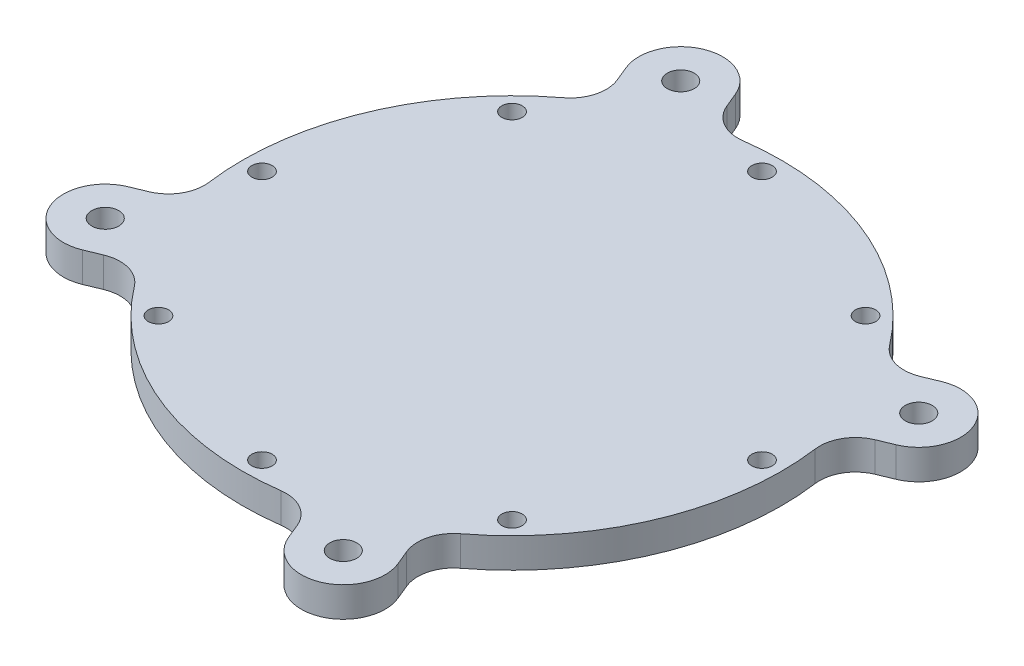
SolidWorks part; units mm, degrees
material "6061-T6 (SS)"
ref_plane "Front Plane" through (0, 0, 0) normal (0, 0, 1) x (1, 0, 0)
ref_plane "Top Plane" through (0, 0, 0) normal (0, 1, 0) x (1, 0, 0)
ref_plane "Right Plane" through (0, 0, 0) normal (1, 0, 0) x (0, 0, -1)
sketch "Sketch1" plane through (0, 0, 0) normal (0, 1, 0) x (1, 0, 0)
  circle A0 centre (0, 0) radius 45
  circle A1 centre (0, 41.75) radius 1.5
  circle A2 centre (29.5217, 29.5217) radius 1.5
  circle A3 centre (41.75, 0) radius 1.5
  circle A4 centre (29.5217, -29.5217) radius 1.5
  circle A5 centre (0, -41.75) radius 1.5
  circle A6 centre (-29.5217, -29.5217) radius 1.5
  circle A7 centre (-41.75, 0) radius 1.5
  circle A8 centre (-29.5217, 29.5217) radius 1.5
  point P22 (0, 0)
  dimension "D1" = 8
extrude "Boss-Extrude2" add sketch "Sketch1" along normal blind 5
sketch "Sketch9" plane through (0, 0, 0) normal (0, -1, 0) x (1, 0, 0)
  circle A2 centre (27, 0) radius 3.937
  circle A3 centre (0, -27) radius 3.937
  circle A4 centre (-27, 0) radius 3.937
  circle A5 centre (0, 27) radius 3.937
  point P15 (0, 0)
  dimension "D1" = 4
extrude "Boss-Extrude7" add sketch "Sketch9" along normal blind 4
sketch "Sketch10" plane through (0, 5, 0) normal (0, 1, 0) x (1, 0, 0)
  circle A0 centre (0, 41.75) radius 1.7
  circle A1 centre (29.5217, 29.5217) radius 1.7
  circle A2 centre (41.75, 0) radius 1.7
  circle A3 centre (29.5217, -29.5217) radius 1.7
  circle A4 centre (0, -41.75) radius 1.7
  circle A5 centre (-29.5217, -29.5217) radius 1.7
  circle A6 centre (-41.75, 0) radius 1.7
  circle A7 centre (-29.5217, 29.5217) radius 1.7
  point P19 (0, 0)
  dimension "D1" = 8
extrude "Cut-Extrude9" cut sketch "Sketch10" against normal blind 14
sketch "Sketch16" plane through (0, 0, 0) normal (0, -1, 0) x (1, 0, 0)
  line L0 (0, 0) -> (45, 0)
  line L1 (0, 0) -> (41.5746, 17.2208)
  line L2 (-58.808, 24.3233) -> (24.3233, 58.808)
  line L3 (-58.808, 24.3233) -> (-24.3233, -58.808)
  line L4 (24.3233, 58.808) -> (58.808, -24.3233)
  line L5 (-24.3233, -58.808) -> (58.808, -24.3233)
  line L6 (-58.808, 24.3233) -> (58.808, -24.3233) construction
  line L7 (24.3233, 58.808) -> (-24.3233, -58.808) construction
  line L8 (0, 0) -> (48.0521, -19.8746)
  line L9 (48.0521, -19.8746) -> (50.7275, -13.406)
  line L10 (50.7275, -13.406) -> (45.3766, -26.3431)
  line L11 (54.6528, -30.1798) -> (60.0037, -17.2427)
  line L12 (54.6528, -30.1798) -> (36.1004, -22.5065)
  line L13 (60.0037, -17.2427) -> (41.4513, -9.5694)
  line L14 (36.1004, -22.5065) -> (41.4513, -9.5694)
  line L15 (54.6528, -30.1798) -> (41.4513, -9.5694) construction
  line L16 (60.0037, -17.2427) -> (36.1004, -22.5065) construction
  circle A0 centre (0, 0) radius 45 construction
  circle A1 centre (48.0521, -19.8746) radius 7
  circle A2 centre (48.0521, -19.8746) radius 2.25
  dimension "D1" = 22.5
  dimension "D2" = 90
  dimension "D3" = 90
  dimension "D4" = 52
extrude "Boss-Extrude8" add sketch "Sketch16" against normal up to surface (5 mm away) contours A1 L12 | A1 L13 | A2 L8 A1 L10 | A2 L10 A1 L8 | A2 L10 A1 region at (42.7047, 0, -13.1821) region at (39.5396, 0, -20.8346) region at (46.3163, 0, -15.6903) region at (43.8678, 0, -21.6103) region at (51.012, 0, -21.0989) up to face at (0, 5, -40.05)
fillet "Fillet1" radius 6 2 edges at (43.7528, 2.5, -10.5213) (38.4019, 2.5, -23.4584)
sketch "Sketch17" plane through (0, 5, 0) normal (0, 1, 0) x (1, 0, 0)
  circle A0 centre (0, 0) radius 8.3177
extrude "Boss-Extrude9" add sketch "Sketch17" along normal blind 10
pattern_circular "CirPattern1" count 4 over 360 about axis through (0, 15, 0) along (0, 1, 0) of "Boss-Extrude8", "Fillet1"
sketch "Sketch18" plane through (0, 0, 0) normal (0, 0, 1) x (1, 0, 0)
  line L1 (8.3177, 15) -> (-8.3177, 15)
  line L2 (8.3177, 15) -> (8.3177, 5)
  line L3 (8.3177, 5) -> (-8.3177, 5)
  line L4 (-8.3177, 15) -> (-8.3177, 5)
  line L5 (-30.937, 0) -> (30.937, 0)
  line L6 (-30.937, 0) -> (-30.937, -4)
  line L7 (-30.937, -4) -> (30.937, -4)
  line L8 (30.937, 0) -> (30.937, -4)
extrude "Cut-Extrude10" cut sketch "Sketch18" against normal through all both and the other way through all
sketch "Sketch19" plane through (0, 0, 0) normal (0, -1, 0) x (1, 0, 0)
  circle A1 centre (-18.4816, 7.6441) radius 1.5
  circle A2 centre (7.6441, 18.4816) radius 1.5
  circle A3 centre (18.4816, -7.6441) radius 1.5
  circle A4 centre (-7.6441, -18.4816) radius 1.5
  dimension "D2" = 4
hole_wizard "M3x0.5 Tapped Hole1" positions "Sketch23" profile "Sketch24" tap size "M3x0.5" standard "ANSI Metric"
sketch "Sketch23" plane through (0, 0, 0) normal (0, -1, 0) x (-1, 0, 0)
  point P0 (-18.4816, 7.6441)
  point P3 (7.6441, 18.4816)
  point P6 (18.4816, -7.6441)
  point P9 (-7.6441, -18.4816)
cosmetic thread "Hole Thread1" parameters "D1"=6, "D2"=3
cosmetic thread "Hole Thread2" parameters "D1"=6, "D2"=3
cosmetic thread "Hole Thread3" parameters "D1"=6, "D2"=3
cosmetic thread "Hole Thread4" parameters "D1"=6, "D2"=3
sketch "Sketch24" plane through (18.4816, 0, -7.6441) normal (1, 0, 0) x (0, 0, -1)
  line L0 (0, 0) -> (0, 4)
  line L1 (0, 4) -> (1.25, 3.2489)
  line L2 (1.25, 3.2489) -> (1.25, 0.275)
  line L3 (1.25, 0.275) -> (1.525, 0)
  line L5 (1.525, 0) -> (0, 0)
  line L6 (-1.25, 0.275) -> (-1.525, 0) construction
  line L10 (0, 4) -> (-1.25, 3.2489) construction
  line L11 (0, -6.35) -> (0, 107.95) construction
  dimension "Tap Drill Dia." = 2.5
  dimension "Tap Drill Depth" = 4
  dimension "Near C'Sink Dia." = 3.05
  dimension "Near C'Sink Angle" = 90
  dimension "Drill Angle" = 118
